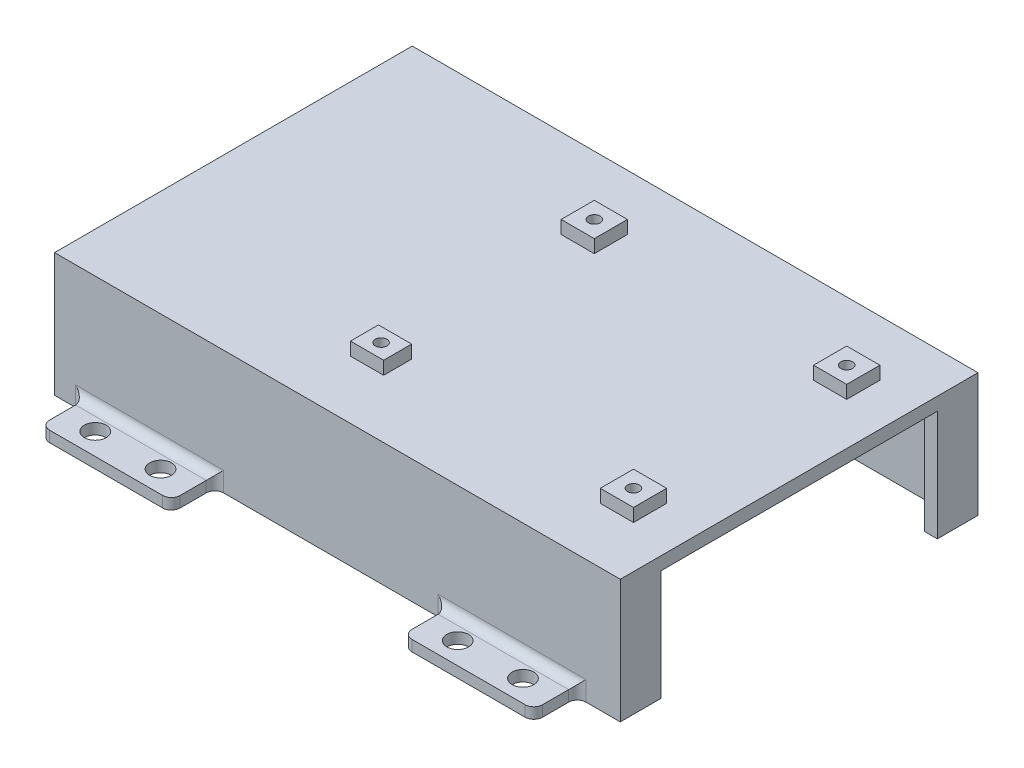
SolidWorks part; units mm, degrees
material "ABS"
ref_plane "Front Plane" through (0, 0, 0) normal (0, 0, 1) x (1, 0, 0)
ref_plane "Top Plane" through (0, 0, 0) normal (0, 1, 0) x (1, 0, 0)
ref_plane "Right Plane" through (0, 0, 0) normal (1, 0, 0) x (0, 0, -1)
sketch "Sketch1" plane through (0, 0, 0) normal (0, 1, 0) x (1, 0, 0)
  line L0 (-303.5027, 0) -> (303.5027, 0) construction
  line L1 (-223.52, -111.125) -> (223.52, -111.125)
  line L2 (-228.6, -106.045) -> (-228.6, 106.045)
  line L3 (-223.52, 111.125) -> (223.52, 111.125)
  line L4 (228.6, -106.045) -> (228.6, 106.045)
  line L5 (-228.6, -111.125) -> (228.6, 111.125) construction
  line L6 (-228.6, 111.125) -> (228.6, -111.125) construction
  line L7 (-303.5027, 36.5125) -> (303.5027, 36.5125) construction
  line L8 (-303.5027, -36.5125) -> (303.5027, -36.5125) construction
  line L9 (127, 111.125) -> (127, -111.125) construction
  line L10 (-142.24, 111.125) -> (-142.24, -111.125) construction
  arc A0 (223.52, 111.125) -> (228.6, 106.045) centre (223.52, 106.045) cw
  arc A1 (223.52, -111.125) -> (228.6, -106.045) centre (223.52, -106.045) ccw
  arc A2 (-223.52, -111.125) -> (-228.6, -106.045) centre (-223.52, -106.045) cw
  arc A3 (-228.6, 106.045) -> (-223.52, 111.125) centre (-223.52, 106.045) cw
  circle A4 centre (127, 36.5125) radius 2.54
  circle A5 centre (127, -36.5125) radius 2.54
  circle A6 centre (-142.24, 36.5125) radius 2.54
  circle A7 centre (-142.24, -36.5125) radius 2.54
  circle A8 centre (209.55, 0) radius 6.35
  point P0 (0, 0)
  point P20 (0, 0)
  point P37 (228.6, 0)
  dimension "D3" = 5.08
  dimension "D7" = 5.08
  dimension "D9" = 12.7
  dimension "D1" = 222.25
  dimension "D2" = 457.2
  dimension "D6" = 269.24
  dimension "D8" = 101.6
  dimension "D10" = 19.05
  dimension "D4" = 36.5125
  dimension "D5" = 36.5125
extrude "mainbaseplate" add sketch "Sketch1" along normal blind 3
sketch "Sketch2" plane through (0, 0, 0) normal (0, -1, 0) x (1, 0, 0)
  circle A0 centre (-142.24, 36.5125) radius 2.54 construction
  circle A1 centre (-142.24, -36.5125) radius 2.54 construction
  circle A2 centre (127, -36.5125) radius 2.54 construction
  circle A3 centre (127, 36.5125) radius 2.54 construction
  circle A4 centre (-142.24, 36.5125) radius 2.54
  circle A5 centre (-142.24, -36.5125) radius 2.54
  circle A6 centre (127, -36.5125) radius 2.54
  circle A7 centre (127, 36.5125) radius 2.54
  circle A8 centre (127, 36.5125) radius 6.096
  circle A9 centre (127, -36.5125) radius 6.096
  circle A10 centre (-142.24, -36.5125) radius 6.096
  circle A11 centre (-142.24, 36.5125) radius 6.096
  dimension "D1" = 12.192
extrude "BaseBoss-Extrude2" [suppressed] add sketch "Sketch2" along normal blind 10.16
sketch "Sketch3" plane through (0, 0, 0) normal (0, -1, 0) x (1, 0, 0)
  line L0 (-228.6, 0) -> (228.6, 0) construction
  line L1 (-228.6, -106.045) -> (-228.6, 106.045) construction
  line L2 (228.6, 106.045) -> (228.6, -106.045) construction
  line L3 (-228.6, 28.4) -> (-73.2, 28.4)
  line L4 (-228.6, -25.4) -> (-76.2, -25.4)
  line L6 (-228.6, 25.4) -> (-76.2, 25.4)
  line L7 (-76.2, -25.4) -> (-76.2, 25.4)
  line L8 (-228.6, -25.4) -> (-76.2, 25.4) construction
  line L9 (-228.6, 25.4) -> (-76.2, -25.4) construction
  line L10 (-73.2, -28.4) -> (-73.2, 28.4)
  line L11 (-228.6, -28.4) -> (-73.2, -28.4)
  line L12 (-228.6, 28.4) -> (-228.6, 25.4)
  line L13 (-228.6, -25.4) -> (-228.6, -28.4)
  point P6 (-152.4, 0)
  dimension "D1" = 50.8
  dimension "D2" = 152.4
  dimension "D3" = 76.2
  dimension "D4" = 3
extrude "Drive BatteryBoss-Extrude1" [suppressed] add sketch "Sketch3" along normal blind 28.575
sketch "Sketch4" [suppressed] plane through (0, -28.575, 0) normal (0, -1, 0) x (1, 0, 0)
  line L1 (-228.6, 28.4) -> (-73.2, 28.4)
  line L2 (-228.6, 28.4) -> (-228.6, -28.4)
  line L3 (-228.6, -28.4) -> (-73.2, -28.4)
  line L4 (-73.2, 28.4) -> (-73.2, -28.4)
extrude "drive Battery CapBoss-Extrude2" [suppressed] add sketch "Sketch4" along normal blind 3
sketch "Sketch5" [suppressed] plane through (0, -31.575, 0) normal (0, -1, 0) x (1, 0, 0)
  line L0 (-98.6, -28.4) -> (-73.2, -3)
  line L1 (-228.6, -28.4) -> (-73.2, -28.4) construction
  line L2 (-73.2, -28.4) -> (-73.2, 28.4) construction
  line L3 (-73.2, -3) -> (-52.1474, -3)
  line L4 (-52.1474, -3) -> (-52.1474, -43.6373)
  line L5 (-52.1474, -43.6373) -> (-98.6, -43.6373)
  line L6 (-98.6, -43.6373) -> (-98.6, -28.4)
  dimension "D1" = 25.4
  dimension "D2" = 25.4
  dimension "D3" = 21.0526
  dimension "D4" = 15.2373
extrude "Drive batterycutoutCut-Extrude1" [suppressed] cut sketch "Sketch5" against normal up to surface (31.575 mm away)
sketch "Sketch6" plane through (0, 3, 0) normal (0, 1, 0) x (1, 0, 0)
  line L0 (-228.6, 0) -> (228.6, 0) construction
  line L1 (-228.6, 106.045) -> (-228.6, -106.045) construction
  line L2 (228.6, -106.045) -> (228.6, 106.045) construction
  line L3 (-63.5, -41.1) -> (66.5, -41.1)
  line L4 (-63.5, -38.1) -> (63.5, -38.1)
  line L6 (-63.5, 38.1) -> (63.5, 38.1)
  line L7 (63.5, -38.1) -> (63.5, 38.1)
  line L8 (-63.5, -38.1) -> (63.5, 38.1) construction
  line L9 (-63.5, 38.1) -> (63.5, -38.1) construction
  line L10 (66.5, -41.1) -> (66.5, 41.1)
  line L11 (-63.5, 41.1) -> (66.5, 41.1)
  line L12 (-63.5, -41.1) -> (-63.5, -38.1)
  line L13 (-63.5, 38.1) -> (-63.5, 41.1)
  point P6 (0, 0)
  dimension "D1" = 127
  dimension "D2" = 76.2
  dimension "D4" = 63.5
  dimension "D3" = 3
extrude "PiBatteryBoxBoss-Extrude3" add sketch "Sketch6" along normal blind 25.4
sketch "Sketch7" plane through (0, 28.4, 0) normal (0, 1, 0) x (1, 0, 0)
  line L1 (66.5, 41.1) -> (-63.5, 41.1)
  line L2 (66.5, 41.1) -> (66.5, -41.1)
  line L3 (66.5, -41.1) -> (-63.5, -41.1)
  line L4 (-63.5, 41.1) -> (-63.5, -41.1)
extrude "PibatterytopBoss-Extrude4" add sketch "Sketch7" along normal blind 3
sketch "Sketch8" plane through (66.5, 0, 0) normal (1, 0, 0) x (0, 0, -1)
  line L0 (-38.1, 28.4) -> (38.1, 3) construction
  line L1 (38.1, 28.4) -> (-38.1, 28.4) construction
  line L2 (-31.75, 3) -> (31.75, 3)
  line L3 (-31.75, 3) -> (-31.75, 28.4)
  line L4 (-31.75, 28.4) -> (31.75, 28.4)
  line L5 (31.75, 3) -> (31.75, 28.4)
  line L6 (-31.75, 3) -> (31.75, 28.4) construction
  line L7 (-31.75, 28.4) -> (31.75, 3) construction
  point P2 (0, 15.7)
  dimension "D1" = 31.75
extrude "pibatterywiresCut-Extrude2" cut sketch "Sketch8" against normal blind 13.16
sketch "Sketch9" plane through (0, 31.4, 0) normal (0, 1, 0) x (1, 0, 0)
  line L0 (-63.5, 41.1) -> (66.5, -41.1) construction
  line L1 (-63.5, 0) -> (66.5, 0) construction
  line L2 (-5.08, -24.489) -> (52.92, -24.489) construction
  line L3 (-5.08, -24.489) -> (-5.08, 24.511) construction
  line L4 (-5.08, 24.511) -> (52.92, 24.511) construction
  line L5 (52.92, -24.489) -> (52.92, 24.511) construction
  line L6 (-5.08, -24.489) -> (52.92, 24.511) construction
  line L7 (-5.08, 24.511) -> (52.92, -24.489) construction
  line L8 (49.11, 20.701) -> (56.73, 20.701)
  line L9 (49.11, 20.701) -> (49.11, 28.321)
  line L10 (49.11, 28.321) -> (56.73, 28.321)
  line L11 (56.73, 20.701) -> (56.73, 28.321)
  line L12 (49.11, 20.701) -> (56.73, 28.321) construction
  line L13 (49.11, 28.321) -> (56.73, 20.701) construction
  line L14 (49.11, -28.299) -> (56.73, -28.299)
  line L16 (49.11, -20.679) -> (56.73, -20.679)
  line L18 (49.11, -28.299) -> (56.73, -20.679) construction
  line L19 (49.11, -20.679) -> (56.73, -28.299) construction
  line L20 (-8.89, 20.701) -> (-1.27, 20.701)
  line L21 (-8.89, 20.701) -> (-8.89, 28.321)
  line L22 (-8.89, 28.321) -> (-1.27, 28.321)
  line L23 (-1.27, 20.701) -> (-1.27, 28.321)
  line L24 (-8.89, 20.701) -> (-1.27, 28.321) construction
  line L25 (-8.89, 28.321) -> (-1.27, 20.701) construction
  line L26 (-8.89, -27.7078) -> (-1.27, -27.7078)
  line L27 (-8.89, -27.7078) -> (-8.89, -21.2702)
  line L28 (-8.89, -21.2702) -> (-1.27, -21.2702)
  line L29 (-1.27, -27.7078) -> (-1.27, -21.2702)
  line L30 (-8.89, -27.7078) -> (-1.27, -21.2702) construction
  line L31 (-8.89, -21.2702) -> (-1.27, -27.7078) construction
  line L32 (-63.5, 41.1) -> (-63.5, -41.1) construction
  line L33 (66.5, -41.1) -> (66.5, 41.1) construction
  line L34 (56.73, -20.679) -> (56.73, -28.299)
  line L35 (49.11, -20.679) -> (49.11, -28.299)
  circle A0 centre (52.92, 24.511) radius 1.35
  circle A1 centre (-5.08, 24.511) radius 1.35
  circle A2 centre (-5.08, -24.489) radius 1.35
  circle A3 centre (52.92, -24.489) radius 1.35
  point P4 (-8.057, 0)
  dimension "D3" = 2.7
  dimension "D4" = 7.62
  dimension "D1" = 58
  dimension "D2" = 49
  dimension "D5" = 7.62
  dimension "D6" = 7.62
  dimension "D7" = 7.62
  dimension "D8" = 7.62
  dimension "D9" = 7.62
  dimension "D10" = 58.42
  dimension "D11" = 24.511
  dimension "D12" = 7.62
extrude "PiBoardBoss-Extrude5" add sketch "Sketch9" along normal blind 3
sketch "Sketch10" plane through (0, 3, 0) normal (0, 1, 0) x (1, 0, 0)
  line L0 (228.6, 0) -> (-228.6, 0) construction
  line L1 (228.6, -106.045) -> (228.6, 106.045) construction
  line L2 (-228.6, 106.045) -> (-228.6, -106.045) construction
  line L3 (104.95, 18.875) -> (174.45, 18.875)
  line L4 (107.95, -15.875) -> (171.45, -15.875)
  line L5 (107.95, -15.875) -> (107.95, -6.175)
  line L6 (107.95, 15.875) -> (171.45, 15.875)
  line L7 (171.45, -15.875) -> (171.45, 15.875)
  line L8 (107.95, -15.875) -> (171.45, 15.875) construction
  line L9 (107.95, 15.875) -> (171.45, -15.875) construction
  line L10 (174.45, -18.875) -> (174.45, 18.875)
  line L11 (104.95, -18.875) -> (174.45, -18.875)
  line L12 (104.95, -18.875) -> (104.95, -6.175)
  line L13 (104.95, 6.175) -> (107.95, 6.175)
  line L14 (104.95, -6.175) -> (107.95, -6.175)
  line L15 (104.95, 6.175) -> (104.95, 18.875)
  line L16 (104.95, -18.875) -> (104.95, 18.875) construction
  line L17 (107.95, 6.175) -> (107.95, 15.875)
  line L18 (107.95, -15.875) -> (107.95, 15.875) construction
  point P6 (139.7, 0)
  dimension "D1" = 31.75
  dimension "D2" = 63.5
  dimension "D3" = 139.7
  dimension "D5" = 12.7
  dimension "D6" = 12.7
  dimension "D4" = 3
extrude "PanTilt-Extrude6" [suppressed] add sketch "Sketch10" along normal blind 53.34
sketch "Sketch11" [suppressed] plane through (0, 56.34, 0) normal (0, 1, 0) x (1, 0, 0)
  line L1 (104.95, 18.875) -> (174.45, 18.875)
  line L2 (104.95, 18.875) -> (104.95, -18.875)
  line L3 (104.95, -18.875) -> (174.45, -18.875)
  line L4 (174.45, 18.875) -> (174.45, -18.875)
extrude "Boss-Extrude7" [suppressed] add sketch "Sketch11" along normal blind 3
sketch "Sketch12" [suppressed] plane through (0, 59.34, 0) normal (0, 1, 0) x (1, 0, 0)
  line L0 (104.95, 0) -> (174.45, 0) construction
  line L1 (104.95, 18.875) -> (104.95, -18.875) construction
  line L2 (174.45, -18.875) -> (174.45, 18.875) construction
  line L3 (118.745, 1.9377) -> (104.95, 1.9377)
  line L4 (118.745, -10.795) -> (160.655, -10.795)
  line L5 (118.745, -10.795) -> (118.745, -1.9901)
  line L6 (118.745, 10.795) -> (160.655, 10.795)
  line L7 (160.655, -10.795) -> (160.655, 10.795)
  line L8 (118.745, -10.795) -> (160.655, 10.795) construction
  line L9 (118.745, 10.795) -> (160.655, -10.795) construction
  line L10 (115.57, -5.08) -> (163.83, -5.08) construction
  line L11 (115.57, -5.08) -> (115.57, 5.08) construction
  line L12 (115.57, 5.08) -> (163.83, 5.08) construction
  line L13 (163.83, -5.08) -> (163.83, 5.08) construction
  line L14 (115.57, -5.08) -> (163.83, 5.08) construction
  line L15 (115.57, 5.08) -> (163.83, -5.08) construction
  line L16 (118.745, -1.9901) -> (104.95, -1.9901)
  line L17 (118.745, 1.9377) -> (118.745, 10.795)
  line L18 (104.95, 1.9377) -> (95.8416, 0)
  line L19 (95.8416, 0) -> (104.95, -1.9901)
  circle A0 centre (163.83, 5.08) radius 2.0193
  circle A1 centre (163.83, -5.08) radius 2.0193
  circle A2 centre (115.57, 5.08) radius 2.0193
  circle A3 centre (115.57, -5.08) radius 2.0193
  point P6 (139.7, 0)
  point P11 (139.7, 0)
  dimension "D5" = 4.0386
  dimension "D1" = 21.59
  dimension "D2" = 41.91
  dimension "D3" = 48.26
  dimension "D4" = 10.16
  dimension "D6" = 1.9377
  dimension "D7" = 1.9901
extrude "Cut-Extrude3" [suppressed] cut sketch "Sketch12" against normal up to surface (56.34 mm away)
sketch "Sketch13" plane through (0, 3, 0) normal (0, 1, 0) x (1, 0, 0)
  line L0 (228.6, 0) -> (-228.6, 0) construction
  line L1 (228.6, -106.045) -> (228.6, 106.045) construction
  line L2 (-228.6, 106.045) -> (-228.6, -106.045) construction
  line L3 (198.12, 0) -> (198.12, 25.4)
  line L4 (198.12, 25.4) -> (172.72, 69.3941)
  line L5 (172.72, 69.3941) -> (136.799, 105.3151)
  line L6 (198.12, 25.4) -> (198.12, 129.9736) construction
  line L7 (172.72, 69.3941) -> (172.72, 97.5573) construction
  line L8 (136.799, 105.3151) -> (-185.781, 105.3151)
  line L9 (-185.781, 105.3151) -> (-221.702, 69.3941)
  line L10 (-221.702, 69.3941) -> (-221.702, 0)
  line L11 (-185.781, 105.3151) -> (-290.6809, 105.3151) construction
  line L12 (195.12, 0) -> (195.12, 24.5962)
  line L13 (195.12, 24.5962) -> (170.3194, 67.552)
  line L14 (170.3194, 67.552) -> (135.5563, 102.3151)
  line L15 (135.5563, 102.3151) -> (-184.5384, 102.3151)
  line L16 (-184.5384, 102.3151) -> (-218.702, 68.1514)
  line L17 (-218.702, 68.1514) -> (-218.702, 0)
  line L18 (172.72, -69.3941) -> (172.72, -97.5573) construction
  line L19 (198.12, -25.4) -> (198.12, -129.9736) construction
  line L20 (-218.702, -68.1514) -> (-218.702, 0)
  line L21 (-184.5384, -102.3151) -> (-218.702, -68.1514)
  line L22 (135.5563, -102.3151) -> (-184.5384, -102.3151)
  line L23 (170.3194, -67.552) -> (135.5563, -102.3151)
  line L24 (195.12, -24.5962) -> (170.3194, -67.552)
  line L25 (195.12, 0) -> (195.12, -24.5962)
  line L26 (-221.702, -69.3941) -> (-221.702, 0)
  line L27 (-185.781, -105.3151) -> (-221.702, -69.3941)
  line L28 (136.799, -105.3151) -> (-185.781, -105.3151)
  line L29 (172.72, -69.3941) -> (136.799, -105.3151)
  line L30 (198.12, -25.4) -> (172.72, -69.3941)
  line L31 (198.12, 0) -> (198.12, -25.4)
  dimension "D1" = 30.48
  dimension "D2" = 25.4
  dimension "D3" = 30
  dimension "D4" = 50.8
  dimension "D5" = 45
  dimension "D6" = 50.8
  dimension "D7" = 322.58
  dimension "D8" = 50.8
  dimension "D9" = 45
  dimension "D10" = 3
extrude "Bottom Shell WallsBoss-Extrude8" [suppressed] add sketch "Sketch13" along normal blind 68.58
sketch "Sketch14" [suppressed] plane through (121.057, 0, -121.057) normal (0.7071, 0, -0.7071) x (-0.7071, 0, -0.7071)
  line L0 (-47.6625, 71.58) -> (-47.6625, 3) construction
  line L1 (-73.0625, 71.58) -> (-22.2625, 71.58) construction
  line L2 (-73.0625, 3) -> (-22.2625, 3) construction
  line L3 (-47.6625, 37.29) -> (-25.0131, 37.29) construction
  circle A0 centre (-47.6625, 64.722) radius 1.3526
  circle A1 centre (-47.6625, 9.858) radius 1.3526
  circle A2 centre (-29.8825, 37.29) radius 4.7625
  point P10 (-47.6625, 37.29)
  dimension "D1" = 2.7051
  dimension "D4" = 9.525
  dimension "D2" = 54.864
  dimension "D3" = 27.432
  dimension "D5" = 17.78
extrude "Sharp1Cut-Extrude4" [suppressed] cut sketch "Sketch14" against normal blind 12.7
sketch "Sketch15" [suppressed] plane through (159.5885, 0, -92.1385) normal (0.866, 0, -0.5) x (-0.5, 0, -0.866)
  line L0 (-51.663, 71.58) -> (-51.663, 3) construction
  line L1 (-77.063, 71.58) -> (-26.263, 71.58) construction
  line L2 (-77.063, 3) -> (-26.263, 3) construction
  line L3 (-51.663, 37.29) -> (-29.7061, 37.29) construction
  circle A0 centre (-51.663, 64.722) radius 1.3526
  circle A1 centre (-51.663, 9.858) radius 1.3526
  circle A2 centre (-33.883, 37.29) radius 4.7625
  point P10 (-51.663, 37.29)
  dimension "D1" = 2.7051
  dimension "D4" = 9.525
  dimension "D2" = 27.432
  dimension "D3" = 54.864
  dimension "D5" = 17.78
extrude "Sharp2Cut-Extrude5" [suppressed] cut sketch "Sketch15" against normal blind 7.62
sketch "Sketch16" [suppressed] plane through (198.12, 0, 0) normal (1, 0, 0) x (0, 0, -1)
  line L0 (0, 71.58) -> (0, 3) construction
  line L1 (-25.4, 71.58) -> (25.4, 71.58) construction
  line L2 (-25.4, 3) -> (25.4, 3) construction
  line L3 (0, 37.29) -> (21.2381, 37.29) construction
  circle A0 centre (0, 64.722) radius 1.3526
  circle A1 centre (0, 9.858) radius 1.3525
  circle A2 centre (17.78, 37.29) radius 4.7625
  dimension "D1" = 2.7051
  dimension "D4" = 9.525
  dimension "D2" = 27.432
  dimension "D3" = 54.864
  dimension "D5" = 17.78
extrude "Sharp3Cut-Extrude6" [suppressed] cut sketch "Sketch16" against normal blind 7.62
sketch "Sketch17" [suppressed] plane through (159.5885, 0, 92.1385) normal (0.866, 0, 0.5) x (0.5, 0, -0.866)
  line L0 (51.663, 71.58) -> (51.663, 3) construction
  line L1 (26.263, 71.58) -> (77.063, 71.58) construction
  line L2 (26.263, 3) -> (77.063, 3) construction
  line L3 (51.663, 37.29) -> (70.4023, 37.29) construction
  circle A0 centre (51.663, 64.722) radius 1.3526
  circle A1 centre (51.663, 9.858) radius 1.3526
  circle A2 centre (69.443, 37.29) radius 4.7625
  dimension "D1" = 2.7051
  dimension "D2" = 2.7051
  dimension "D3" = 9.525
  dimension "D4" = 17.78
  dimension "D5" = 27.432
  dimension "D6" = 54.864
extrude "SharpCut-Extrude7" [suppressed] cut sketch "Sketch17" against normal blind 7.62
sketch "Sketch18" [suppressed] plane through (121.057, 0, 121.057) normal (0.7071, 0, 0.7071) x (0.7071, 0, -0.7071)
  line L0 (47.6625, 71.58) -> (47.6625, 3) construction
  line L1 (22.2625, 71.58) -> (73.0625, 71.58) construction
  line L2 (22.2625, 3) -> (73.0625, 3) construction
  line L3 (25.604, 37.29) -> (69.7209, 37.29) construction
  circle A0 centre (47.6625, 64.722) radius 1.3526
  circle A1 centre (47.6625, 9.858) radius 1.3526
  circle A2 centre (65.4425, 37.29) radius 4.7625
  point P13 (47.6625, 37.29)
  dimension "D1" = 9.525
  dimension "D3" = 2.7051
  dimension "D4" = 2.7051
  dimension "D2" = 17.78
  dimension "D5" = 27.432
  dimension "D6" = 54.864
extrude "SharpCut-Extrude8" [suppressed] cut sketch "Sketch18" against normal blind 7.62
sketch "Sketch19" [suppressed] plane through (0, 71.58, 0) normal (0, 1, 0) x (1, 0, 0)
  line L0 (-223.52, -111.125) -> (223.52, -111.125) construction
  line L1 (228.6, -106.045) -> (228.6, 106.045) construction
  line L2 (223.52, 111.125) -> (-223.52, 111.125) construction
  line L3 (104.95, -111.125) -> (223.52, -111.125)
  line L4 (228.6, -106.045) -> (228.6, 106.045)
  line L5 (223.52, 111.125) -> (104.95, 111.125)
  line L6 (104.95, 111.125) -> (104.95, -111.125)
  arc A0 (223.52, -111.125) -> (228.6, -106.045) centre (223.52, -106.045) ccw construction
  arc A1 (228.6, 106.045) -> (223.52, 111.125) centre (223.52, 106.045) ccw construction
  arc A2 (223.52, -111.125) -> (228.6, -106.045) centre (223.52, -106.045) ccw
  arc A3 (228.6, 106.045) -> (223.52, 111.125) centre (223.52, 106.045) ccw
extrude "TopSensorplateBoss-Extrude8" [suppressed] add sketch "Sketch19" along normal blind 3
sketch "Sketch21" [suppressed] plane through (0, 74.58, 0) normal (0, 1, 0) x (1, 0, 0)
  line L0 (104.95, -18.875) -> (174.45, -18.875) construction
  line L1 (174.45, -18.875) -> (174.45, 18.875) construction
  line L2 (174.45, 18.875) -> (104.95, 18.875) construction
  line L3 (104.95, -18.875) -> (164.29, -18.875)
  line L4 (174.45, -8.715) -> (174.45, 8.715)
  line L5 (164.29, 18.875) -> (104.95, 18.875)
  line L6 (104.95, 18.875) -> (84.8462, 2.2825)
  line L7 (84.8462, 2.2825) -> (104.95, -18.875)
  arc A0 (164.29, -18.875) -> (174.45, -8.715) centre (164.29, -8.715) ccw
  arc A1 (174.45, 8.715) -> (164.29, 18.875) centre (164.29, 8.715) ccw
  circle A2 centre (127, -36.5125) radius 6.096 construction
  circle A3 centre (127, 36.5125) radius 6.096 construction
  circle A4 centre (127, -36.5125) radius 6.096
  circle A5 centre (127, 36.5125) radius 6.096
  dimension "D1" = 10.16
extrude "topsensorplateCut-Extrude4" [suppressed] cut sketch "Sketch21" against normal blind 8.08
sketch "Sketch22" [suppressed] plane through (0, 0, 0) normal (0, -1, 0) x (1, 0, 0)
  line L0 (228.6, 0) -> (-228.6, 0) construction
  line L1 (228.6, 106.045) -> (228.6, -106.045) construction
  line L2 (-228.6, 28.4) -> (-228.6, -28.4) construction
  line L3 (220.98, 0) -> (220.98, 76.2)
  line L4 (220.98, 76.2) -> (193.675, 103.505)
  line L5 (193.675, 103.505) -> (-25.4, 103.505)
  line L6 (-223.52, 111.125) -> (223.52, 111.125) construction
  line L7 (217.98, 0) -> (217.98, 74.9574)
  line L8 (217.98, 74.9574) -> (192.4324, 100.505)
  line L9 (192.4324, 100.505) -> (-25.4, 100.505)
  line L10 (-25.4, 103.505) -> (-25.4, 100.505)
  line L11 (217.98, 0) -> (217.98, -74.9574)
  line L12 (220.98, 0) -> (220.98, -76.2)
  line L13 (-25.4, -103.505) -> (-25.4, -100.505)
  line L14 (192.4324, -100.505) -> (-25.4, -100.505)
  line L15 (217.98, -74.9574) -> (192.4324, -100.505)
  line L16 (193.675, -103.505) -> (-25.4, -103.505)
  line L17 (220.98, -76.2) -> (193.675, -103.505)
  line L18 (-220.98, 28.4) -> (-220.98, 76.2)
  line L19 (-73.2, 28.4) -> (-228.6, 28.4) construction
  line L20 (-220.98, 76.2) -> (-193.548, 103.505)
  line L21 (-193.548, 103.505) -> (-127, 103.505)
  line L22 (-228.6, 28.4) -> (-228.6, 106.045) construction
  line L23 (-217.98, 28.4) -> (-217.98, 74.9533)
  line L24 (-217.98, 74.9533) -> (-192.3094, 100.505)
  line L25 (-192.3094, 100.505) -> (-127, 100.505)
  line L26 (-127, 103.505) -> (-127, 100.505)
  line L27 (-220.98, 28.4) -> (-217.98, 28.4)
  line L28 (-127, -103.505) -> (-127, -100.505)
  line L29 (-192.3094, -100.505) -> (-127, -100.505)
  line L30 (-217.98, -74.9533) -> (-192.3094, -100.505)
  line L31 (-217.98, -28.4) -> (-217.98, -74.9533)
  line L32 (-193.548, -103.505) -> (-127, -103.505)
  line L33 (-220.98, -76.2) -> (-193.548, -103.505)
  line L34 (-220.98, -28.4) -> (-220.98, -76.2)
  line L35 (-220.98, -28.4) -> (-217.98, -28.4)
  dimension "D1" = 7.62
  dimension "D2" = 7.62
  dimension "D3" = 76.2
  dimension "D4" = 34.925
  dimension "D5" = 254
  dimension "D7" = 7.62
  dimension "D8" = 76.2
  dimension "D9" = 7.62
  dimension "D10" = 101.6
  dimension "D11" = 35.052
  dimension "D6" = 3
  dimension "D12" = 3
extrude "frontrockerpanBoss-Extrude9" [suppressed] add sketch "Sketch22" along normal blind 45.72
sketch "Sketch23" [suppressed] plane through (0, 0, -103.505) normal (0, 0, -1) x (-1, 0, 0)
  line L0 (25.4, 0) -> (-193.675, 0) construction
  line L2 (-223.1134, -81.0052) -> (22.7571, -81.0052) construction
  line L3 (22.7571, -81.0052) -> (254.0819, -81.0052) construction
  circle A1 centre (-127, -81.0052) radius 63.5
  circle A2 centre (152.4, -81.0052) radius 63.5
  dimension "D1" = 81.0052
  dimension "D4" = 127
  dimension "D2" = 22.7571
  dimension "D3" = 223.1134
  dimension "D5" = 127
  dimension "D6" = 279.4
extrude "TireCut-Extrude5" [suppressed] cut sketch "Sketch23" against normal blind 25.4
sketch "Sketch24" [suppressed] plane through (-221.702, 0, 0) normal (-1, 0, 0) x (0, 0, 1)
  line L0 (-69.3941, 71.58) -> (69.3941, 3) construction
  circle A0 centre (0, 37.29) radius 10.9855
  dimension "D1" = 21.971
extrude "Cut-Extrude6" [suppressed] cut sketch "Sketch24" against normal blind 7.62
sketch "Sketch25" [suppressed] plane through (0, 71.58, 0) normal (0, 1, 0) x (1, 0, 0)
  line L3 (-223.52, -111.125) -> (223.52, -111.125) construction
  line L5 (-228.6, 106.045) -> (-228.6, -106.045) construction
  line L6 (223.52, 111.125) -> (-223.52, 111.125) construction
  line L7 (-223.52, -111.125) -> (-147.32, -111.125)
  line L8 (-228.6, 106.045) -> (-228.6, -106.045)
  line L9 (-147.32, 111.125) -> (-223.52, 111.125)
  line L10 (-147.32, 111.125) -> (-147.32, -111.125)
  arc A2 (-228.6, -106.045) -> (-223.52, -111.125) centre (-223.52, -106.045) ccw construction
  arc A3 (-223.52, 111.125) -> (-228.6, 106.045) centre (-223.52, 106.045) ccw construction
  arc A4 (-228.6, -106.045) -> (-223.52, -111.125) centre (-223.52, -106.045) ccw
  arc A5 (-223.52, 111.125) -> (-228.6, 106.045) centre (-223.52, 106.045) ccw
  dimension "D1" = 147.32
extrude "ReartopdeckBoss-Extrude10" [suppressed] add sketch "Sketch25" along normal blind 3
sketch "Sketch28" [suppressed] plane through (0, 0, 103.505) normal (0, 0, 1) x (1, 0, 0)
  line L0 (-205.194, -45.72) -> (-93.1399, -108.4782)
  line L1 (-93.1399, -108.4782) -> (179.794, -45.72)
  line L2 (74.206, -45.72) -> (-102.0458, -69.7467)
  line L3 (-102.0458, -69.7467) -> (-127, -22.8065)
  arc A0 (-192.3094, -31.6141) -> (-205.194, -45.72) centre (-152.4, -81.0052) ccw construction
  arc A1 (-127, -22.8065) -> (-192.3094, -31.6141) centre (-152.4, -81.0052) ccw construction
  arc A2 (179.794, -45.72) -> (74.206, -45.72) centre (127, -81.0052) ccw construction
  arc A3 (-192.3094, -31.6141) -> (-205.194, -45.72) centre (-152.4, -81.0052) ccw
  arc A4 (-127, -22.8065) -> (-192.3094, -31.6141) centre (-152.4, -81.0052) ccw
  arc A5 (179.794, -45.72) -> (74.206, -45.72) centre (127, -81.0052) ccw
extrude "TireCut-Extrude8" [suppressed] cut sketch "Sketch28" against normal blind 35.56
sketch "Sketch30" [suppressed] plane through (0, 74.58, 0) normal (0, 1, 0) x (1, 0, 0)
  line L0 (-147.32, 0) -> (-228.6, 0) construction
  line L1 (-147.32, -111.125) -> (-147.32, 111.125) construction
  line L2 (-228.6, 106.045) -> (-228.6, -106.045) construction
  circle A0 centre (-166.37, 0) radius 6.35
  dimension "D1" = 12.7
  dimension "D2" = 19.05
extrude "Cut-Extrude10" [suppressed] cut sketch "Sketch30" against normal blind 11.684
sketch "Sketch31" [suppressed] plane through (0, 0, 0) normal (1, 0, 0) x (0, 0, -1)
  line L0 (102.3151, 71.58) -> (102.3151, 3) construction
  line L1 (-102.3151, 71.58) -> (-76.9151, 71.58)
  line L2 (-102.3151, 71.58) -> (-102.3151, 68.58)
  line L3 (-102.3151, 68.58) -> (-76.9151, 68.58)
  line L4 (102.3151, 71.58) -> (102.3151, 68.58)
  line L5 (-76.9151, 71.58) -> (-76.9151, 68.58)
  line L6 (76.9151, 71.58) -> (76.9151, 68.58)
  line L7 (76.9151, 71.58) -> (102.3151, 71.58)
  line L8 (76.9151, 68.58) -> (102.3151, 68.58)
  dimension "D1" = 3
  dimension "D2" = 25.4
  dimension "D3" = 25.4
extrude "Boss-Extrude8" [suppressed] add sketch "Sketch31" along normal blind 134.62 and the other way blind 180.34
sketch "Sketch32" plane through (0, 0, 0) normal (0, -1, 0) x (1, 0, 0)
  line L1 (-362.1056, 298.8668) -> (350.2899, 298.8668)
  line L2 (-362.1056, 298.8668) -> (-362.1056, -225.3293)
  line L3 (-362.1056, -225.3293) -> (350.2899, -225.3293)
  line L4 (350.2899, 298.8668) -> (350.2899, -225.3293)
extrude "Cut-Extrude11" cut sketch "Sketch32" against normal up to surface (3 mm away) up to face at (22.1667, 3, -36.9833)
sketch "Sketch33" plane through (0, 3, 0) normal (0, -1, 0) x (1, 0, 0)
  line L0 (-63.5, 41.1) -> (66.5, 41.1) construction
  line L1 (-56.639, 41.1) -> (-26.639, 41.1)
  line L2 (-56.639, 41.1) -> (-56.639, 51.1)
  line L3 (-56.639, 51.1) -> (-26.639, 51.1)
  line L4 (-26.639, 41.1) -> (-26.639, 51.1)
  line L6 (-56.639, 46.1) -> (-41.639, 46.1) construction
  line L7 (-41.639, 51.1) -> (-41.639, 41.1) construction
  line L8 (0, 0) -> (102.0774, 0) construction
  line L9 (0, 0) -> (0, 79.069) construction
  line L10 (56.639, 51.1) -> (26.639, 51.1)
  line L11 (26.639, 41.1) -> (26.639, 51.1)
  line L12 (56.639, 41.1) -> (26.639, 41.1)
  line L13 (56.639, 41.1) -> (56.639, 51.1)
  line L14 (56.639, -41.1) -> (56.639, -51.1)
  line L15 (56.639, -41.1) -> (26.639, -41.1)
  line L16 (26.639, -41.1) -> (26.639, -51.1)
  line L17 (56.639, -51.1) -> (26.639, -51.1)
  line L18 (-56.639, -51.1) -> (-26.639, -51.1)
  line L19 (-26.639, -41.1) -> (-26.639, -51.1)
  line L20 (-56.639, -41.1) -> (-26.639, -41.1)
  line L21 (-56.639, -41.1) -> (-56.639, -51.1)
  circle A0 centre (-49.139, 46.1) radius 2.5
  circle A1 centre (-34.139, 46.1) radius 2.5
  circle A2 centre (34.139, 46.1) radius 2.5
  circle A3 centre (49.139, 46.1) radius 2.5
  circle A4 centre (-49.139, -46.1) radius 2.5
  circle A5 centre (-34.139, -46.1) radius 2.5
  circle A6 centre (49.139, -46.1) radius 2.5
  circle A7 centre (34.139, -46.1) radius 2.5
  dimension "D3" = 5
  dimension "D1" = 10
  dimension "D2" = 30
extrude "Boss-Extrude9" add sketch "Sketch33" against normal blind 2.5
fillet "Fillet2" radius 2 20 edges at (-56.639, 4.25, -51.1) (-26.639, 4.25, -51.1) (-26.639, 4.25, -41.1) (-41.639, 5.5, -41.1) (-56.639, 4.25, -41.1) (26.639, 4.25, -41.1) (56.639, 4.25, -51.1) (26.639, 4.25, -51.1) (41.639, 5.5, -41.1) (56.639, 4.25, -41.1) (56.639, 4.25, 51.1) (26.639, 4.25, 51.1) (-26.639, 4.25, 51.1) (-56.639, 4.25, 51.1) (-26.639, 4.25, 41.1) (-56.639, 4.25, 41.1) (-41.639, 5.5, 41.1) (56.639, 4.25, 41.1) (26.639, 4.25, 41.1) (41.639, 5.5, 41.1)
extrude "Cut-Extrude12" cut sketch "Sketch9<2>" against normal blind 5 contours A3 | A2 | A1 | A0 region at (52.92, 31.4, -24.511) region at (-5.08, 31.4, -24.511) region at (-5.08, 31.4, 24.489) region at (52.92, 31.4, 24.489)
sketch "Sketch9<2>" plane through (0, 31.4, 0) normal (0, 1, 0) x (1, 0, 0) same geometry as "Sketch9"
